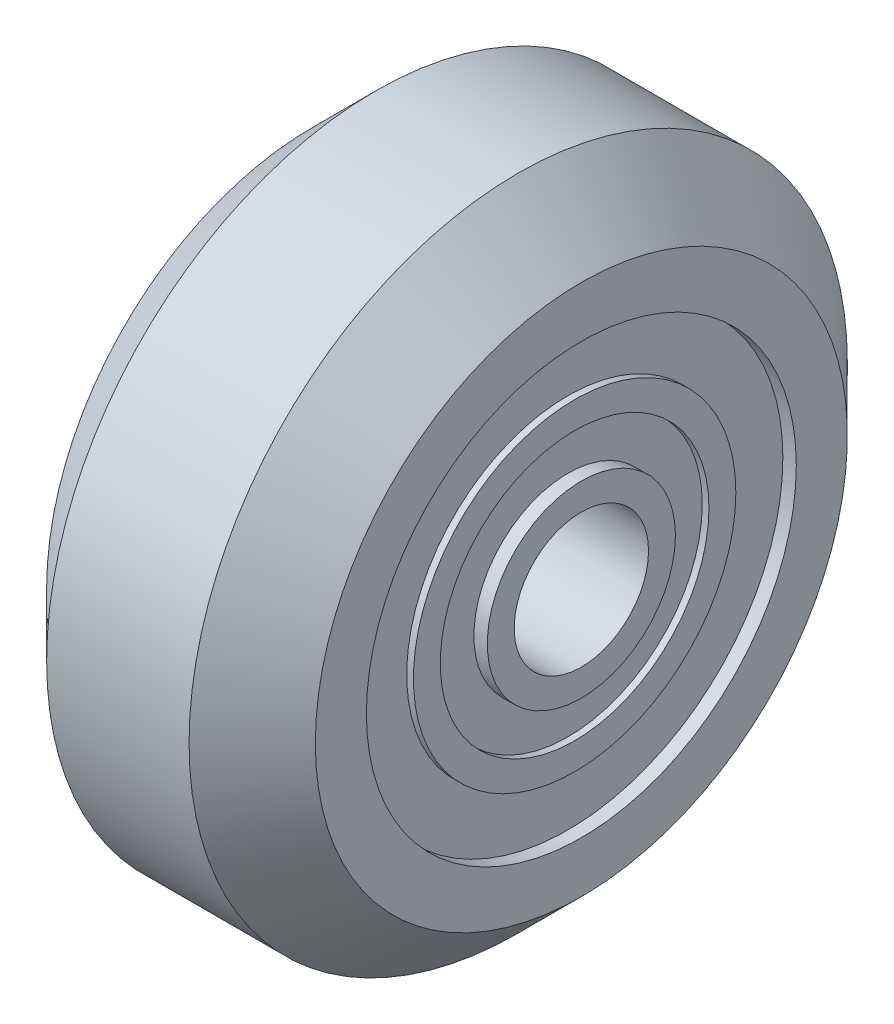
SolidWorks part; units mm, degrees
ref_plane "Front Plane" through (0, 0, 0) normal (0, 0, 1) x (1, 0, 0)
ref_plane "Top Plane" through (0, 0, 0) normal (0, 1, 0) x (1, 0, 0)
ref_plane "Right Plane" through (0, 0, 0) normal (1, 0, 0) x (0, 0, -1)
sketch "Sketch2" plane through (0, 0, 0) normal (0, 0, 1) x (1, 0, 0)
  line L0 (-45.586, 0) -> (46.8419, 0) construction
  line L1 (-5, 8) -> (-5, 9.9)
  line L2 (-5, 9.9) -> (-2.65, 12.25)
  line L3 (-2.65, 12.25) -> (2.65, 12.25)
  line L6 (-5, 8) -> (5, 8)
  line L7 (0, 58.1442) -> (0, -32.0233) construction
  line L8 (5, 9.9) -> (2.65, 12.25)
  line L9 (5, 8) -> (5, 9.9)
  point P8 (0, 8)
  point P13 (0, 8)
  point P14 (0, 12.25)
  dimension "D1" = 5
  dimension "D2" = 225
  dimension "D3" = 12.25
  dimension "D4" = 9.9
  dimension "D5" = 8
revolve "Revolve1" add sketch "Sketch2" angle 360 about L0
sketch "Sketch3" plane through (0, 0, 0) normal (1, 0, 0) x (0, 0, -1)
  circle A1 centre (0, 0) radius 8 construction
  circle A2 centre (0, 0) radius 8
  circle A3 centre (0, 0) radius 6
  circle A4 centre (0, 0) radius 2.5
  circle A5 centre (0, 0) radius 5
  circle A6 centre (0, 0) radius 3.5
  dimension "D1" = 2
  dimension "D2" = 5
  dimension "D3" = 1
  dimension "D4" = 1
extrude "Boss-Extrude1" add sketch "Sketch3" along normal mid plane 9 contours A2 A3 region at (0, 0, 7.7737)
extrude "Boss-Extrude3" add sketch "Sketch3<4>" along normal mid plane 9.5 contours A3 A5 region at (0, 0, 5.8303)
sketch "Sketch3<4>" plane through (0, 0, 0) normal (1, 0, 0) x (0, 0, -1) same geometry as "Sketch3"
extrude "Boss-Extrude4" add sketch "Sketch3<5>" along normal mid plane 9 contours A5 A6 region at (0, 0, 4.8586)
sketch "Sketch3<5>" plane through (0, 0, 0) normal (1, 0, 0) x (0, 0, -1) same geometry as "Sketch3"
extrude "Boss-Extrude5" add sketch "Sketch3<6>" along normal mid plane 10 contours A6 A4 region at (0, 0, 3.401)
sketch "Sketch3<6>" plane through (0, 0, 0) normal (1, 0, 0) x (0, 0, -1) same geometry as "Sketch3"
